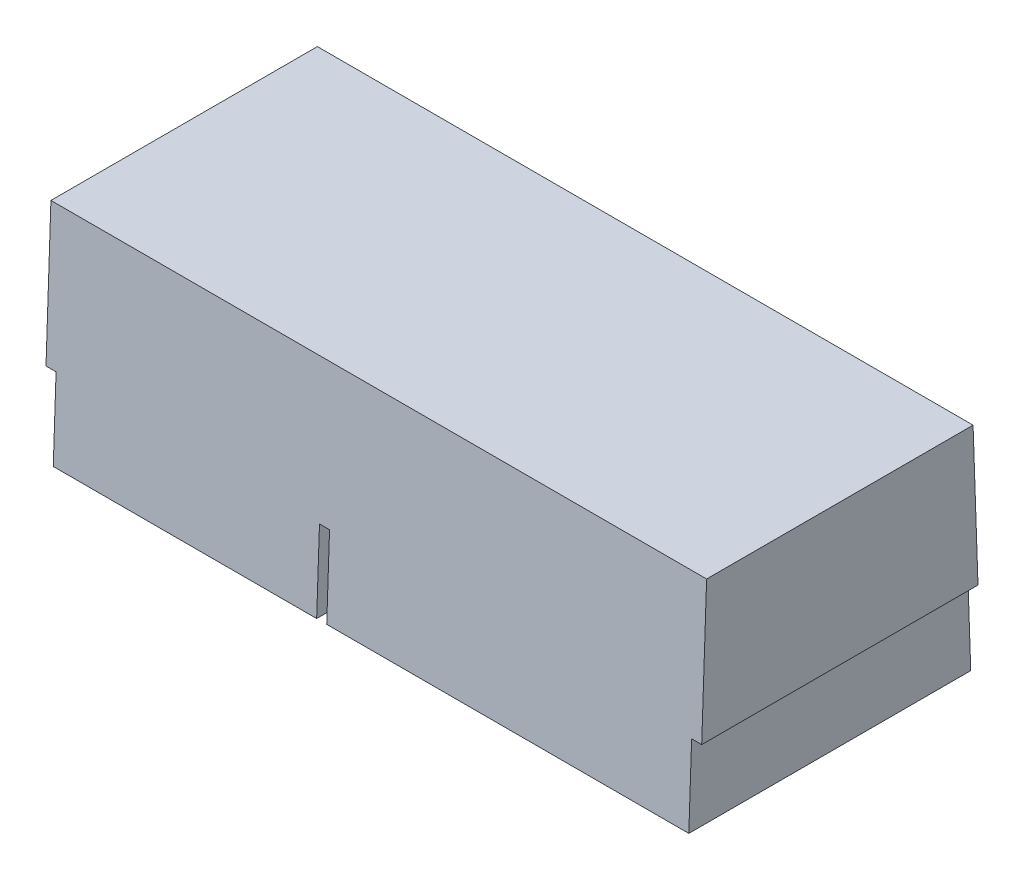
SolidWorks part; units mm, degrees
ref_plane "Front Plane" through (0, 0, 0) normal (0, 0, 1) x (1, 0, 0)
ref_plane "Top Plane" through (0, 0, 0) normal (0, 1, 0) x (1, 0, 0)
ref_plane "Right Plane" through (0, 0, 0) normal (1, 0, 0) x (0, 0, -1)
sketch "Sketch1" plane through (0, 0, 0) normal (1, 0, 0) x (0, 0, -1)
  line L0 (0, 0) -> (0, 38.9723) construction
  line L1 (-17.0647, 0) -> (26.7862, 0) construction
  line L2 (-44.45, -34.925) -> (44.45, -34.925)
  line L3 (44.45, -34.925) -> (42.0108, 34.925)
  line L4 (42.0108, 34.925) -> (-42.0108, 34.925)
  line L5 (-42.0108, 34.925) -> (-44.45, -34.925)
  dimension "D1" = 92
  dimension "D2" = 88.9
  dimension "D3" = 69.85
extrude "Boss-Extrude1" add sketch "Sketch1" along normal blind 206.756
sketch "Sketch2" plane through (206.756, 0, 0) normal (1, 0, 0) x (0, 0, -1)
  line L0 (-43.563, -9.525) -> (43.563, -9.525)
  line L1 (-42.0108, 34.925) -> (-44.45, -34.925) construction
  line L2 (44.45, -34.925) -> (42.0108, 34.925) construction
  line L3 (-43.563, -9.525) -> (-44.45, -34.925)
  line L4 (-44.45, -34.925) -> (44.45, -34.925)
  line L5 (44.45, -34.925) -> (43.563, -9.525)
  dimension "D1" = 25.4
extrude "Cut-Extrude1" cut sketch "Sketch2" against normal blind 3.175
extrude "Cut-Extrude2" cut sketch "Sketch2<2>" along normal blind 3.175 from surface starting at face at (0, 0, 0)
sketch "Sketch2<2>" plane through (206.756, 0, 0) normal (1, 0, 0) x (0, 0, -1) same geometry as "Sketch2"
extrude "Cut-Extrude4" cut sketch "Sketch2<3>" against normal blind 3.175 from offset 117.348 offset against normal yes
sketch "Sketch2<3>" plane through (206.756, 0, 0) normal (1, 0, 0) x (0, 0, -1) same geometry as "Sketch2"
